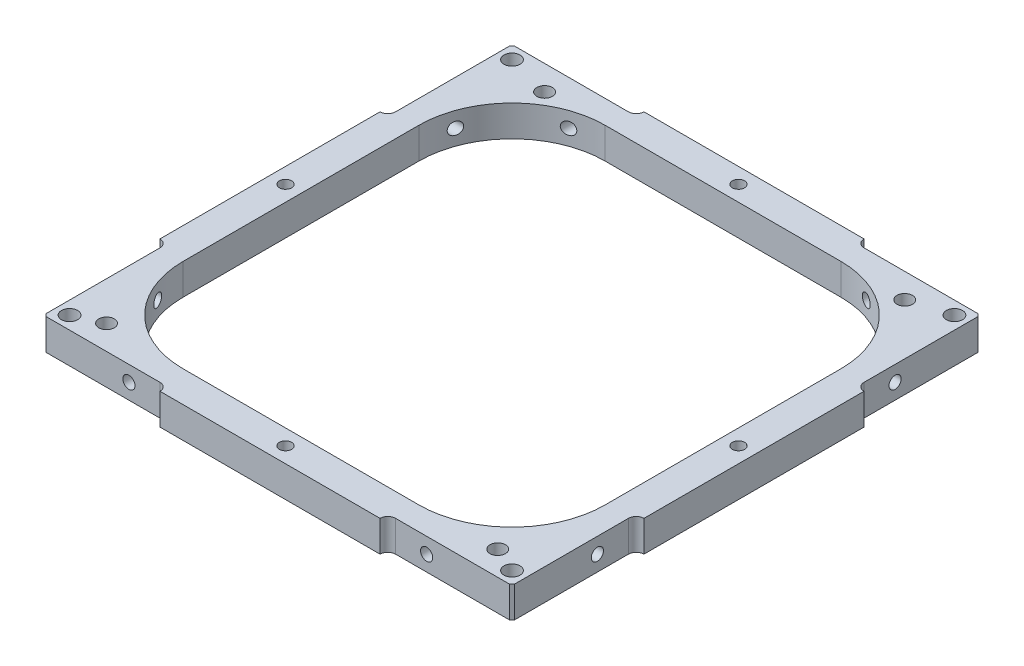
SolidWorks part; units mm, degrees
material "6061-T6 (SS)"
ref_plane "Front Plane" through (0, 0, 0) normal (0, 0, 1) x (1, 0, 0)
ref_plane "Top Plane" through (0, 0, 0) normal (0, 1, 0) x (1, 0, 0)
ref_plane "Right Plane" through (0, 0, 0) normal (1, 0, 0) x (0, 0, -1)
sketch "Sketch1" plane through (0, 0, 0) normal (0, 1, 0) x (1, 0, 0)
  line L0 (-49.5, 22.5125) -> (-47.9125, 22.5125)
  line L1 (-49.5, -49.5) -> (49.5, -49.5)
  line L2 (-49.5, -49.5) -> (-49.5, 49.5)
  line L3 (-49.5, 49.5) -> (49.5, 49.5)
  line L4 (49.5, -49.5) -> (49.5, 49.5)
  line L5 (-49.5, -49.5) -> (49.5, 49.5) construction
  line L6 (-49.5, 49.5) -> (49.5, -49.5) construction
  line L7 (-47.9125, 22.5125) -> (-47.9125, 47.9125)
  line L8 (-47.9125, 47.9125) -> (-22.5125, 47.9125)
  line L9 (-22.5125, 47.9125) -> (-22.5125, 49.5)
  line L10 (22.5125, 49.5) -> (22.5125, 47.9125)
  line L11 (22.5125, 47.9125) -> (47.9125, 47.9125)
  line L12 (47.9125, 47.9125) -> (47.9125, 22.5125)
  line L13 (47.9125, 22.5125) -> (49.5, 22.5125)
  line L14 (49.5, -22.5125) -> (47.9125, -22.5125)
  line L15 (47.9125, -22.5125) -> (47.9125, -47.9125)
  line L16 (47.9125, -47.9125) -> (22.5125, -47.9125)
  line L17 (22.5125, -47.9125) -> (22.5125, -49.5)
  line L18 (-22.5125, -49.5) -> (-22.5125, -47.9125)
  line L19 (-22.5125, -47.9125) -> (-47.9125, -47.9125)
  line L20 (-47.9125, -47.9125) -> (-47.9125, -22.5125)
  line L21 (-47.9125, -22.5125) -> (-49.5, -22.5125)
  point P0 (0, 0)
  dimension "D1" = 99
  dimension "D2" = 99
  dimension "D3" = 26.9875
  dimension "D4" = 1.5875
  dimension "D5" = 26.9875
  dimension "D6" = 1.5875
extrude "Boss-Extrude1" add sketch "Sketch1" along normal blind 6.35 contours L21 L20 L19 L18 L1 L17 L16 L15 L14 L4 L13 L12 L11 L10 L3 L9 L8 L7 L0 L2 region at (0, 0, 0)
chamfer "Chamfer1" distance 0.508 angle 45 4 edges at (47.9125, 3.175, -47.9125) (-47.9125, 3.175, -47.9125) (-47.9125, 3.175, 47.9125) (47.9125, 3.175, 47.9125)
fillet "Fillet1" radius 1.5875 8 edges at (-47.9125, 3.175, -22.5125) (-22.5125, 3.175, -47.9125) (22.5125, 3.175, -47.9125) (47.9125, 3.175, -22.5125) (47.9125, 3.175, 22.5125) (22.5125, 3.175, 47.9125) (-22.5125, 3.175, 47.9125) (-47.9125, 3.175, 22.5125)
hole_wizard "M4x0.7 Tapped Hole2" positions "Sketch2" profile "Sketch3" tap size "M4x0.7" standard "ANSI Metric" end condition through all
sketch "Sketch2" plane through (0, 0, 0) normal (0, -1, 0) x (-1, 0, 0)
  line L0 (-49.5, -22.5125) -> (-49.5, 22.5125) construction
  line L1 (22.5125, 49.5) -> (-22.5125, 49.5) construction
  line L5 (49.5, -22.5125) -> (49.5, 22.5125) construction
  line L6 (22.5125, -49.5) -> (-22.5125, -49.5) construction
  point P0 (-45.25, 45.25)
  point P2 (45.25, 45.25)
  point P4 (45.25, -45.25)
  point P6 (-45.25, -45.25)
  dimension "D1" = 4.25
  dimension "D2" = 4.25
  dimension "D3" = 4.25
  dimension "D4" = 4.25
  dimension "D5" = 4.25
  dimension "D6" = 4.25
  dimension "D7" = 4.25
  dimension "D8" = 4.25
sketch "Sketch3" plane through (45.25, 0, -45.25) normal (1, 0, 0) x (0, 0, -1)
  line L0 (0, 0) -> (0, 6.35)
  line L1 (0, 6.35) -> (1.65, 6.35)
  line L2 (1.65, 6.35) -> (1.65, 0)
  line L5 (1.65, 0) -> (0, 0)
  line L11 (0, -6.35) -> (0, 107.95) construction
  dimension "Thru Tap Drill Dia." = 3.3
  dimension "Thru Tap Drill Depth" = 6.35
cosmetic thread "Hole Thread6" parameters "D2"=4
cosmetic thread "Hole Thread7" parameters "D2"=4
cosmetic thread "Hole Thread8" parameters "D2"=4
cosmetic thread "Hole Thread9" parameters "D2"=4
hole_wizard "M3x0.5 Tapped Hole1" positions "Sketch6" profile "Sketch7" tap size "M3x0.5" standard "ANSI Metric"
sketch "Sketch6" plane through (0, 0, 47.9125) normal (0, 0, 1) x (1, 0, 0)
  line L1 (-24.1, 0) -> (-47.4045, 0) construction
  line L4 (47.4045, 0) -> (24.1, 0) construction
  line L5 (-24.1, 0) -> (-24.1, 6.35) construction
  line L7 (24.1, 6.35) -> (24.1, 0) construction
  point P0 (-30.45, 3.175)
  point P2 (30.45, 3.175)
  dimension "D1" = 6.35
  dimension "D2" = 3.175
  dimension "D3" = 6.35
  dimension "D4" = 3.175
sketch "Sketch7" plane through (-30.45, 3.175, 47.9125) normal (1, 0, 0) x (0, -1, 0)
  line L0 (0, 0) -> (0, 8.3711)
  line L1 (0, 8.3711) -> (1.25, 7.62)
  line L2 (1.25, 7.62) -> (1.25, 0)
  line L5 (1.25, 0) -> (0, 0)
  line L10 (0, 8.3711) -> (-1.25, 7.62) construction
  line L11 (0, -6.35) -> (0, 107.95) construction
  dimension "Tap Drill Dia." = 2.5
  dimension "Tap Drill Depth" = 7.62
  dimension "Drill Angle" = 118
cosmetic thread "Hole Thread1" parameters "D1"=4.7625, "D2"=3
cosmetic thread "Hole Thread2" parameters "D1"=4.7625, "D2"=3
ref_plane "Plane1" through (0, 0, 0) normal (0, 0, 1) x (1, 0, 0)
ref_plane "Plane2" through (0, 0, 0) normal (-1, 0, 0) x (0, 0, 1)
ref_axis "Axis1" through (0, -0.3175, 0) along (0, 1, 0)
pattern_circular "CirPattern1" count 4 over 360 about axis through (0, -0.3175, 0) along (0, 1, 0) of "M3x0.5 Tapped Hole1"
sketch "Sketch9" plane through (0, 6.35, 0) normal (0, 1, 0) x (1, 0, 0)
  line L0 (0, 3.4925) -> (0, -3.4925) construction
  line L1 (-3.4925, 0) -> (3.4925, 0) construction
  circle A0 centre (-40.005, -42.926) radius 1.5875
  circle A1 centre (40.005, -42.926) radius 1.5875
  circle A2 centre (37.465, 42.8625) radius 1.5875
  circle A3 centre (-36.195, 42.8625) radius 1.5875
  dimension "D7" = 3.175
  dimension "D4" = 73.66
  dimension "D1" = 40.005
  dimension "D2" = 40.005
  dimension "D3" = 2.54
  dimension "D5" = 42.8625
  dimension "D6" = 42.926
extrude "Cut-Extrude2" cut sketch "Sketch9" against normal through all
sketch "Sketch11" plane through (0, 6.35, 0) normal (0, 1, 0) x (1, 0, 0)
  line L0 (-22.5125, 49.5) -> (22.5125, 49.5) construction
  line L1 (-43.15, -43.15) -> (43.15, -43.15)
  line L2 (-43.15, -43.15) -> (-43.15, 43.15)
  line L3 (-43.15, 43.15) -> (43.15, 43.15)
  line L4 (43.15, -43.15) -> (43.15, 43.15)
  line L5 (-43.15, -43.15) -> (43.15, 43.15) construction
  line L6 (-43.15, 43.15) -> (43.15, -43.15) construction
  line L7 (49.5, -22.5125) -> (49.5, 22.5125) construction
  line L8 (-44.2725, 42.0275) -> (42.0275, -44.2725)
  line L9 (-42.0275, -44.2725) -> (44.2725, 42.0275)
  line L10 (-42.0275, 44.2725) -> (44.2725, -42.0275)
  line L11 (-44.2725, -42.0275) -> (42.0275, 44.2725)
  circle A5 centre (-36.195, 42.8625) radius 4.7625
  circle A6 centre (-36.195, 42.8625) radius 4.7625
  circle A9 centre (37.465, 42.8625) radius 4.7625
  circle A10 centre (37.465, 42.8625) radius 4.7625
  circle A12 centre (-40.005, -42.926) radius 4.7625
  circle A13 centre (-40.005, -42.926) radius 4.7625
  circle A14 centre (0, 0) radius 25.4
  circle A15 centre (40.005, -42.926) radius 4.7625
  circle A16 centre (40.005, -42.926) radius 4.7625
  circle A17 centre (0, 0) radius 22.225
  point P0 (0, 0)
  dimension "D9" = 50.8
  dimension "D1" = 6.35
  dimension "D2" = 6.35
  dimension "D3" = 3.175
  dimension "D4" = 3.175
  dimension "D5" = 3.175
  dimension "D6" = 3.175
  dimension "D7" = 1.5875
  dimension "D8" = 1.5875
  dimension "D10" = 3.175
hole_wizard "M3x0.5 Tapped Hole3" positions "Sketch14" profile "Sketch15" tap size "M3x0.5" standard "ANSI Metric"
sketch "Sketch14" plane through (0, 6.35, 0) normal (0, 1, 0) x (1, 0, 0)
  line L0 (0, 3.4925) -> (0, -3.4925) construction
  line L1 (-22.5125, -49.5) -> (22.5125, -49.5) construction
  point P0 (0, -46.325)
  dimension "D1" = 3.175
sketch "Sketch15" plane through (0, 6.35, 46.325) normal (1, 0, 0) x (0, 0, 1)
  line L0 (0, 0) -> (0, 8.3711)
  line L1 (0, 8.3711) -> (1.25, 7.62)
  line L2 (1.25, 7.62) -> (1.25, 0)
  line L5 (1.25, 0) -> (0, 0)
  line L10 (0, 8.3711) -> (-1.25, 7.62) construction
  line L11 (0, -6.35) -> (0, 107.95) construction
  dimension "Tap Drill Dia." = 2.5
  dimension "Tap Drill Depth" = 7.62
  dimension "Drill Angle" = 118
cosmetic thread "Hole Thread5" parameters "D1"=6.35, "D2"=4
sketch "Sketch16" plane through (0, 6.35, 0) normal (0, 1, 0) x (1, 0, 0)
  line L0 (-22.5125, 49.5) -> (22.5125, 49.5) construction
  line L1 (-43.15, -43.15) -> (43.15, -43.15)
  line L2 (-43.15, -43.15) -> (-43.15, 43.15)
  line L3 (-43.15, 43.15) -> (43.15, 43.15)
  line L4 (43.15, -43.15) -> (43.15, 43.15)
  line L5 (-43.15, -43.15) -> (43.15, 43.15) construction
  line L6 (-43.15, 43.15) -> (43.15, -43.15) construction
  line L7 (49.5, -22.5125) -> (49.5, 22.5125) construction
  arc A0 (24.1, 43.15) -> (43.15, 24.1) centre (24.1, 24.1) cw
  arc A1 (43.15, -24.1) -> (24.1, -43.15) centre (24.1, -24.1) cw
  arc A2 (-24.1, -43.15) -> (-43.15, -24.1) centre (-24.1, -24.1) cw
  arc A3 (-43.15, 24.1) -> (-24.1, 43.15) centre (-24.1, 24.1) cw
  circle A4 centre (37.465, 42.8625) radius 3.9859 construction
  circle A5 centre (37.465, 42.8625) radius 1.5875 construction
  point P0 (0, 0)
  dimension "D3" = 19.05
  dimension "D1" = 6.35
  dimension "D2" = 6.35
extrude "Cut-Extrude3" cut sketch "Sketch16" against normal through all contours A3 L2 A2 L1 A1 L4 A0 L3 region at (0, 6.35, 0)
pattern_circular "CirPattern2" count 4 over 360 about axis through (0, -0.3175, 0) along (0, 1, 0) of "M3x0.5 Tapped Hole3"
sketch "Sketch17" plane through (0, 6.35, 0) normal (0, 1, 0) x (1, 0, 0)
  circle A0 centre (-36.195, 42.8625) radius 3.25
  circle A1 centre (37.465, 42.8625) radius 3.25
  circle A2 centre (40.005, -42.926) radius 3.25
  circle A3 centre (-40.005, -42.926) radius 3.25
  dimension "D1" = 6.5
  dimension "D2" = 6.5
  dimension "D3" = 6.5
  dimension "D4" = 6.5
sketch "Sketch19" plane through (0, 6.35, 0) normal (0, 1, 0) x (1, 0, 0)
  line L0 (45.25, 45.25) -> (45.25, -45.25) construction
  line L1 (45.25, -45.25) -> (-45.25, -45.25) construction
  line L2 (-45.25, -45.25) -> (-45.25, 45.25) construction
  line L3 (-45.25, 45.25) -> (45.25, 45.25) construction
  circle A0 centre (-42.25, 45.25) radius 0.5
  circle A1 centre (-45.25, 42.25) radius 0.5
  circle A2 centre (42.25, 45.25) radius 0.5
  circle A3 centre (45.25, 42.25) radius 0.5
  circle A4 centre (45.25, -42.25) radius 0.5
  circle A5 centre (42.25, -45.25) radius 0.5
  circle A6 centre (-45.25, -42.25) radius 0.5
  circle A7 centre (-42.25, -45.25) radius 0.5
  circle A8 centre (-45.25, 45.25) radius 3 construction
  circle A9 centre (45.25, 45.25) radius 3 construction
  circle A10 centre (45.25, -45.25) radius 3 construction
  circle A11 centre (-45.25, -45.25) radius 3 construction
  dimension "D1" = 1
  dimension "D2" = 6
